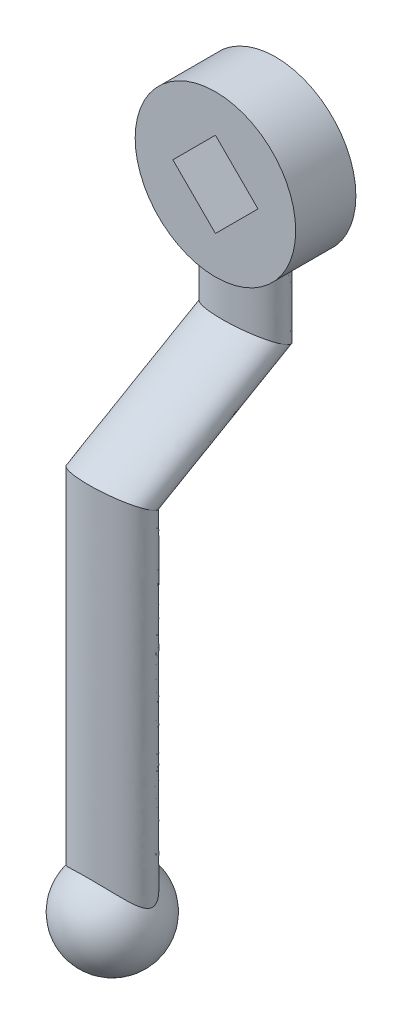
SolidWorks part; units mm, degrees
ref_plane "Front Plane" through (0, 0, 0) normal (1, 0, 0) x (0, 1, 0)
ref_plane "Top Plane" through (0, 0, 0) normal (0, 0, 1) x (0, 1, 0)
ref_plane "Right Plane" through (0, 0, 0) normal (0, 1, 0) x (-1, 0, 0)
sketch "Sketch1" plane through (0, 0, 0) normal (0, 0, 1) x (0, 1, 0)
  circle A0 centre (0, 0) radius 12
  dimension "D1" = 24
extrude "Boss-Extrude1" add sketch "Sketch1" along normal blind 4.5 and the other way blind 4.5
sketch "Sketch2" plane through (0, 0, 0) normal (1, 0, 0) x (0, 1, 0)
  line L0 (0, 0) -> (-20, 0)
  line L1 (-20, 0) -> (-31.5, 19.9186)
  line L2 (-31.5, 19.9186) -> (-86.5, 19.9186)
sketch "Sketch3" plane through (0, 0, 0) normal (0, 1, 0) x (-1, 0, 0)
  ellipse E0 centre (0, 0) end of major axis (6, 0) minor radius 3.5
sweep "Sweep1" add profiles "Sketch3" path "Sketch2"
sketch "Sketch4" plane through (0, -86.5, 0) normal (0, -1, 0) x (1, 0, 0)
  line L0 (0, 26.9186) -> (0, 12.9186)
  arc A0 (0, 12.9186) -> (0, 26.9186) centre (0, 19.9186) ccw
  dimension "D1" = 14
revolve "Revolve1" add sketch "Sketch4" angle 360 about L0
sketch "Sketch5" plane through (0, 0, 4.5) normal (0, 0, 1) x (1, 0, 0)
  line L1 (0, 6.364) -> (-6.364, 0)
  line L2 (-6.364, 0) -> (0, -6.364)
  line L3 (0, -6.364) -> (6.364, 0)
  line L4 (6.364, 0) -> (0, 6.364)
  circle A0 centre (0, 0) radius 4.5 construction
  dimension "D1" = 9
extrude "Cut-Extrude1" cut sketch "Sketch5" against normal up to next
